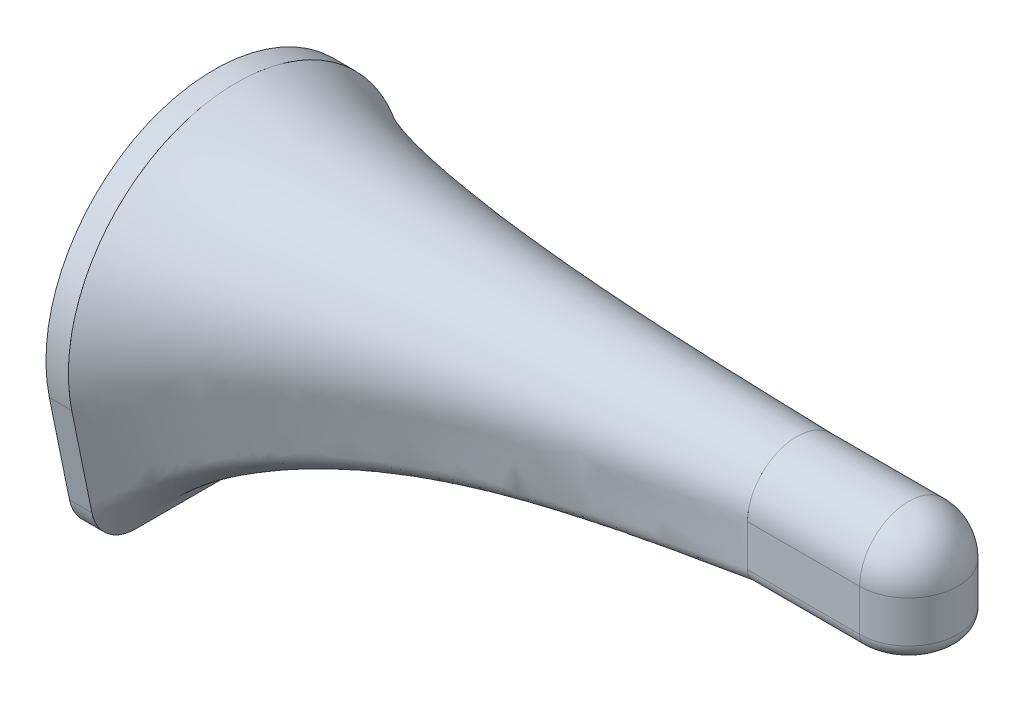
SolidWorks part; units mm, degrees
ref_plane "Front Plane" through (0, 0, 0) normal (0, 0, 1) x (1, 0, 0)
ref_plane "Top Plane" through (0, 0, 0) normal (0, 1, 0) x (1, 0, 0)
ref_plane "Right Plane" through (0, 0, 0) normal (1, 0, 0) x (0, 0, -1)
sketch "Sketch2" plane through (0, 0, 0) normal (1, 0, 0) x (0, 0, -1)
  line L22 (-68, 0) -> (68, 0)
  line L23 (-67.5278, -8) -> (67.5278, -8)
  line L24 (67.5278, -8) -> (57.6447, -57.6)
  line L25 (-67.5278, -8) -> (-57.6447, -57.6)
  line L26 (-44.9073, -68) -> (44.8918, -68)
  line L27 (-73.4847, -15) -> (-64.5032, -59)
  line L28 (-44.9073, -75) -> (44.9073, -75)
  line L29 (64.5032, -59) -> (73.4847, -15)
  arc A16 (-68, 0) -> (68, 0) centre (0, 0) cw
  arc A17 (-57.6447, -57.6) -> (-44.9073, -68) centre (-44.9073, -55) ccw
  arc A18 (44.8918, -68) -> (57.6447, -57.6) centre (44.9677, -55.074) ccw
  arc A19 (-73.4847, -15) -> (73.4847, -15) centre (0, 0) cw
  arc A20 (-64.5032, -59) -> (-44.9073, -75) centre (-44.9073, -55) ccw
  arc A21 (44.9073, -75) -> (64.5032, -59) centre (44.9073, -55) ccw
  point P20 (0, 0)
ref_plane "Plane3" through (5, 0, 0) normal (1, 0, 0) x (0, 0, -1)
sketch "Sketch6" plane through (5, 0, 0) normal (1, 0, 0) x (0, 0, -1)
  line L17 (-66.1362, -13.5) -> (-58.0529, -53.1)
  line L18 (-40.4166, -67.5) -> (40.4166, -67.5)
  line L19 (58.0529, -53.1) -> (66.1362, -13.5)
  arc A13 (-66.1362, -13.5) -> (66.1362, -13.5) centre (0, 0) cw
  arc A14 (-58.0529, -53.1) -> (-40.4166, -67.5) centre (-40.4166, -49.5) ccw
  arc A15 (40.4166, -67.5) -> (58.0529, -53.1) centre (40.4166, -49.5) ccw
ref_plane "Plane2" through (50, 0, 0) normal (1, 0, 0) x (0, 0, -1)
sketch "Sketch8" plane through (50, 0, 0) normal (1, 0, 0) x (0, 0, -1)
  line L0 (-49.6022, 6.9508) -> (-43.5397, -22.7492)
  line L1 (-30.3124, -33.5492) -> (30.3124, -33.5492)
  line L2 (43.5397, -22.7492) -> (49.6022, 6.9508)
  arc A0 (-49.6022, 6.9508) -> (49.6022, 6.9508) centre (0, 17.0758) cw
  arc A1 (-43.5397, -22.7492) -> (-30.3124, -33.5492) centre (-30.3124, -20.0492) ccw
  arc A2 (30.3124, -33.5492) -> (43.5397, -22.7492) centre (30.3124, -20.0492) ccw
ref_plane "Plane1" through (250, 0, 0) normal (1, 0, 0) x (0, 0, -1)
sketch "Sketch3" plane through (250, 0, 0) normal (1, 0, 0) x (0, 0, -1)
  line L0 (-30, 7.5) -> (-30, -7.5)
  line L1 (5, 32.5) -> (-5, 32.5)
  line L2 (-5, -32.5) -> (5, -32.5)
  line L3 (0, 82.8389) -> (0, -82.8389) construction
  line L4 (30, 7.5) -> (30, -7.5)
  arc A0 (-30, 7.5) -> (-5, 32.5) centre (-5, 7.5) cw
  arc A1 (-30, -7.5) -> (-5, -32.5) centre (-5, -7.5) ccw
  arc A2 (30, -7.5) -> (5, -32.5) centre (5, -7.5) cw
  arc A3 (30, 7.5) -> (5, 32.5) centre (5, 7.5) ccw
  point P5 (-30, 0)
  point P11 (0, 32.5)
  point P21 (0, -32.5)
  dimension "D1" = 25
  dimension "D2" = 15
  dimension "D3" = 30
sketch "Sketch5" plane through (50, 0, 0) normal (1, 0, 0) x (0, 0, -1)
  line L0 (-60, 17.5) -> (-60, -17.5)
  line L1 (10, 67.5) -> (-10, 67.5)
  line L2 (-10, -67.5) -> (10, -67.5)
  line L3 (60, 17.5) -> (60, -17.5)
  line L4 (-60, 0) -> (60, 0) construction
  arc A0 (-60, 17.5) -> (-10, 67.5) centre (-10, 17.5) cw
  arc A1 (-60, -17.5) -> (-10, -67.5) centre (-10, -17.5) ccw
  arc A2 (60, -17.5) -> (10, -67.5) centre (10, -17.5) cw
  arc A3 (60, 17.5) -> (10, 67.5) centre (10, 17.5) ccw
  point P7 (0, 67.5)
  point P14 (0, -67.5)
  point P15 (0, 0)
  point P19 (0, 0)
  dimension "D1" = 50
  dimension "D2" = 35
  dimension "D3" = 20
sketch "Sketch9" plane through (250, 0, 0) normal (1, 0, 0) x (0, 0, -1)
  line L0 (-21.9062, 41.2765) -> (-21.9062, 22.714)
  line L1 (-15.1562, 15.964) -> (15.1562, 15.964)
  line L2 (21.9062, 22.714) -> (21.9062, 41.2765)
  arc A0 (-21.9062, 41.2765) -> (21.9062, 41.2765) centre (0, 41.2765) cw
  arc A1 (-21.9062, 22.714) -> (-15.1562, 15.964) centre (-15.1562, 22.714) ccw
  arc A2 (15.1562, 15.964) -> (21.9062, 22.714) centre (15.1562, 22.714) ccw
extrude "Boss-Extrude1" add sketch "Sketch2" against normal blind 10
surface "Surface-Loft3" start constraint default end constraint default
sketch "Sketch2<7>" plane through (0, 0, 0) normal (1, 0, 0) x (0, 0, -1) same geometry as "Sketch2"
ref_plane "Plane4" through (300, 0, 0) normal (1, 0, 0) x (0, 0, -1)
sketch "Sketch11" plane through (300, 0, 0) normal (1, 0, 0) x (0, 0, -1)
  line L0 (-21.9062, 41.285) -> (-21.9062, 22.7225)
  line L1 (-15.1562, 15.9725) -> (15.1562, 15.9725)
  line L2 (21.9062, 22.7225) -> (21.9062, 41.285)
  line L3 (16.9062, 22.7225) -> (16.9062, 41.285)
  line L4 (-15.1562, 20.9725) -> (15.1562, 20.9725)
  line L5 (-16.9062, 41.285) -> (-16.9062, 22.7225)
  arc A0 (-21.9062, 41.285) -> (21.9062, 41.285) centre (0, 41.285) cw
  arc A1 (-21.9062, 22.7225) -> (-15.1562, 15.9725) centre (-15.1562, 22.7225) ccw
  arc A2 (15.1562, 15.9725) -> (21.9062, 22.7225) centre (15.1562, 22.7225) ccw
  arc A3 (-16.9062, 41.285) -> (16.9062, 41.285) centre (0, 41.285) cw
  arc A4 (15.1562, 20.9725) -> (16.9062, 22.7225) centre (15.1562, 22.7225) ccw
  arc A5 (-16.9062, 22.7225) -> (-15.1562, 20.9725) centre (-15.1562, 22.7225) ccw
  dimension "D1" = 5
extrude "Boss-Extrude2" add sketch "Sketch11" against normal blind 50 separate body
sketch "Sketch12" plane through (300, 0, 0) normal (1, 0, 0) x (0, 0, -1)
  line L0 (0, 20.9725) -> (-15.1562, 20.9725)
  line L1 (-15.1562, 20.9725) -> (15.1562, 20.9725) construction
  line L2 (-16.9062, 22.7225) -> (-16.9062, 41.285)
  line L3 (0, 15.9725) -> (-15.1562, 15.9725)
  line L4 (-15.1562, 15.9725) -> (15.1562, 15.9725) construction
  line L5 (-21.9062, 22.7225) -> (-21.9062, 41.285)
  line L6 (0, 58.1912) -> (0, 63.1912)
  line L7 (0, 20.9725) -> (0, 15.9725)
  arc A0 (-15.1562, 20.9725) -> (-16.9062, 22.7225) centre (-15.1562, 22.7225) cw
  arc A1 (-15.1562, 15.9725) -> (-21.9062, 22.7225) centre (-15.1562, 22.7225) cw
  arc A2 (-21.9062, 41.285) -> (0, 63.1912) centre (0, 41.285) cw
  arc A3 (21.9062, 41.285) -> (-21.9062, 41.285) centre (0, 41.285) ccw construction
  arc A4 (-16.9062, 41.285) -> (0, 58.1912) centre (0, 41.285) cw
  arc A5 (16.9062, 41.285) -> (-16.9062, 41.285) centre (0, 41.285) ccw construction
revolve "Revolve1" add sketch "Sketch12" angle 180 about L6
